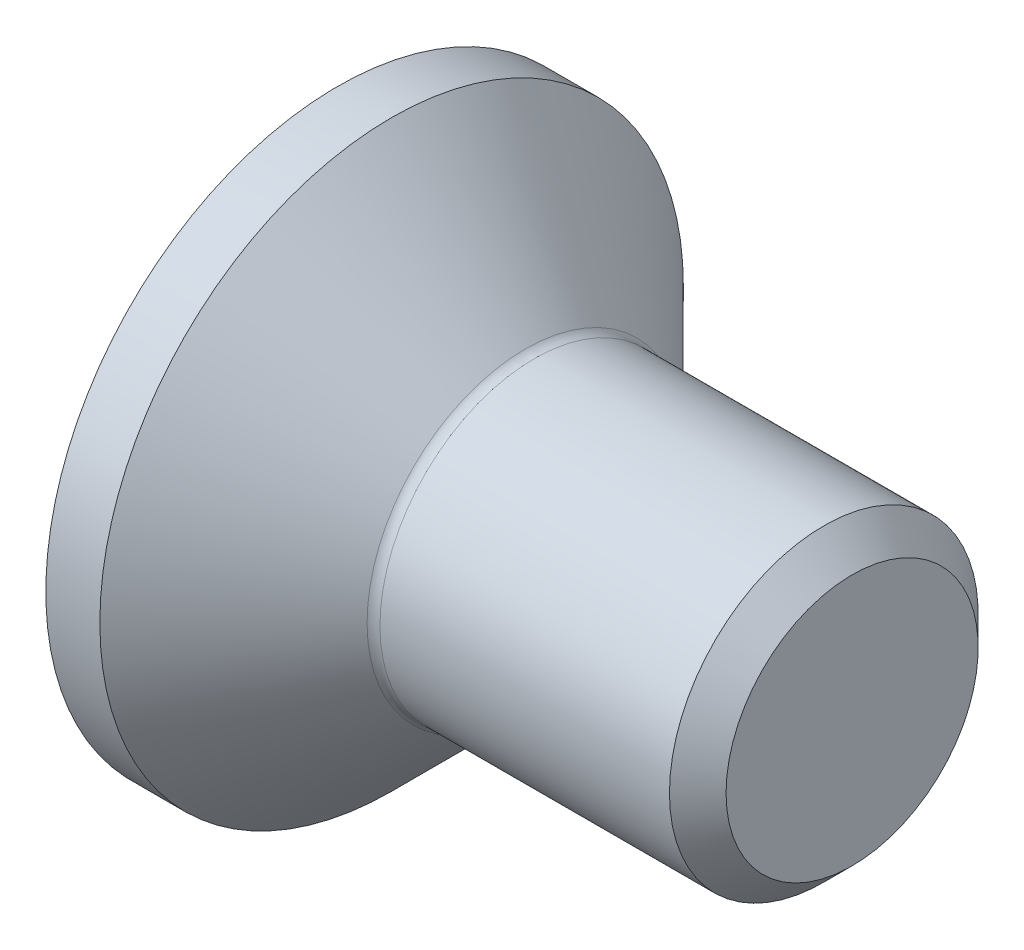
SolidWorks part; units mm, degrees
ref_plane "Front" through (0, 0, 0) normal (0, 0, 1) x (1, 0, 0)
ref_plane "Top" through (0, 0, 0) normal (0, 1, 0) x (1, 0, 0)
ref_plane "Right" through (0, 0, 0) normal (1, 0, 0) x (0, 0, -1)
sketch "Sketch1" plane through (0, 0, 0) normal (0, 0, 1) x (1, 0, 0)
  line L0 (0, 0) -> (0, 6.72)
  line L1 (0, 6.72) -> (3.72, 3)
  line L2 (3.72, 3) -> (10, 3)
  line L3 (10, 3) -> (10, 0)
  line L4 (10, 0) -> (0, 0)
  line L5 (-0.5871, 0) -> (5.4927, 0) construction
  dimension "D1" = 45
revolve "Base" add sketch "Sketch1" angle 360 about L5
cosmetic thread "ThreadCosmetic1" [suppressed] parameters "b"=4.64, "D2"=4.9
sketch "Sketch2" plane through (0, 0, 0) normal (1, 0, 0) x (0, 0, -1)
  line L1 (2.3094, 0) -> (1.1547, 2)
  line L2 (1.1547, 2) -> (-1.1547, 2)
  line L3 (-1.1547, 2) -> (-2.3094, 0)
  line L4 (-2.3094, 0) -> (-1.1547, -2)
  line L5 (-1.1547, -2) -> (1.1547, -2)
  line L6 (1.1547, -2) -> (2.3094, 0)
  circle A0 centre (0, 0) radius 2 construction
  dimension "s" = 4
extrude "HexagonSocket" cut sketch "Sketch2" along normal blind 1.1
sketch "Sketch3" plane through (0, 0, 0) normal (0, 0, 1) x (1, 0, 0)
  line L0 (-0.4391, 0) -> (4.425, 0) construction
  line L1 (1.1, 0) -> (1.1, -2) construction
  line L2 (1.1, 2) -> (2.2547, 0)
  line L3 (2.2547, 0) -> (1.1, -2) construction
  line L4 (1.1, 2) -> (1.1, 0)
  line L5 (1.1, 0) -> (2.2547, 0)
  line L7 (1.1, 2) -> (1.1, 0) construction
  dimension "D1" = 120
revolve "Cut-Revolve1" cut sketch "Sketch3" angle 360 about L0
fillet "HeadFillet" radius 0.25 1 edges at (3.72, 0, 3)
chamfer "Chamfer" distance 0.55 angle 45 1 edges at (10, 0, 3)
sketch "Sketch4" plane through (0, 0, 0) normal (0, 1, 0) x (1, 0, 0)
  line L0 (11.8531, 0) -> (-2.694, 0) construction
  line L1 (-2, 10.67) -> (3, 10.67)
  line L2 (-2, 10.67) -> (-2, 5.67)
  line L3 (-2, 5.67) -> (3, 5.67)
  line L4 (3, 10.67) -> (3, 5.67)
  line L5 (0, 6.72) -> (0, -6.72) construction
  dimension "dk" = 11.34
  dimension "D2" = 2
  dimension "D3" = 5
  dimension "D4" = 5
revolve "Cut-Revolve2" cut sketch "Sketch4" angle 360 about L0
sketch "Sketch5" plane through (0, 0, 0) normal (0, 0, 1) x (1, 0, 0)
  line L0 (9.45, 2.5237) -> (9.725, 3)
  line L1 (9.725, 3) -> (9.725, 3.55)
  line L2 (9.725, 3.55) -> (9.175, 3.55)
  line L3 (9.175, 3.55) -> (9.175, 3)
  line L4 (9.175, 3) -> (9.45, 2.5237)
  line L5 (0, 0) -> (10.6885, 0) construction
  line L6 (9.45, 3) -> (9.45, -3) construction
  dimension "D1" = 6
  dimension "D2" = 0.55
revolve "Cut-Revolve10" [suppressed] cut sketch "Sketch5" angle 360 about L5
pattern_linear "LPattern10" [suppressed] count 7 spacing 0.66 along (-1, 0, 0) of bodies 105
equation "\"D1@Chamfer\" = (  \"d@Sketch1\" - \"D2@ThreadCosmetic1\" )  / 2"
equation "\"D1@Sketch5\" = \"d@Sketch1\""
equation "\"D2@Sketch5\" =  ( \"d@Sketch1\" - \"D2@ThreadCosmetic1\" )  / 2"
equation "\"D3@LPattern10\" = \"D2@Sketch5\" * 1.2"
equation "\"D1@LPattern10\" = \"b@ThreadCosmetic1\" / \"D3@LPattern10\""
